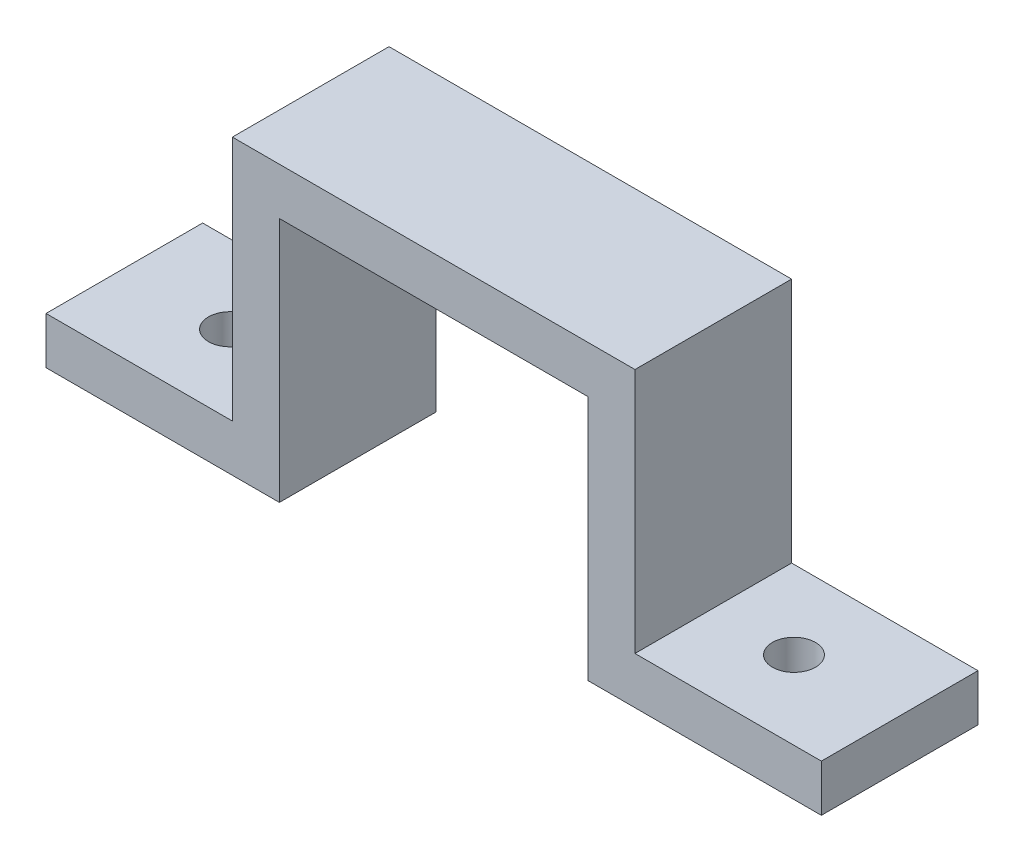
SolidWorks part; units mm, degrees
ref_plane "Front Plane" through (0, 0, 0) normal (0, 0, 1) x (1, 0, 0)
ref_plane "Top Plane" through (0, 0, 0) normal (0, 1, 0) x (1, 0, 0)
ref_plane "Right Plane" through (0, 0, 0) normal (1, 0, 0) x (0, 0, -1)
sketch "Sketch1" plane through (0, 0, 0) normal (0, 1, 0) x (1, 0, 0)
  line L0 (34.6, 0) -> (49.5, 0)
  line L1 (0, 0) -> (14.9, 0)
  line L2 (0, 0) -> (0, -10)
  line L3 (0, -10) -> (14.9, -10)
  line L4 (49.5, 0) -> (49.5, -10)
  line L5 (34.6, -10) -> (49.5, -10)
  line L6 (34.6, 0) -> (34.6, -10)
  line L11 (34.6, 0) -> (37.6, 0)
  line L12 (37.6, 0) -> (37.6, -10)
  line L13 (37.6, -10) -> (34.6, -10)
  line L21 (11.8988, 0) -> (11.8988, -10)
  line L22 (14.9, 0) -> (11.8988, 0)
  line L23 (14.9, 0) -> (14.9, -10)
  line L24 (11.8988, -10) -> (14.9, -10)
  circle A0 centre (6.75, -5) radius 1.375
  circle A1 centre (42.75, -5) radius 1.375
  dimension "D4" = 2.75
  dimension "D1" = 49.5
  dimension "D2" = 10
  dimension "D3" = 19.7
  dimension "D5" = 14.9
  dimension "D6" = 14.9
  dimension "D7" = 3.0012
  dimension "D8" = 3
extrude "Boss-Extrude1" add sketch "Sketch1" along normal blind 3 contours L1 L2 L3 A0 | L0 L12 L5 L4 A1 region at (43.55, 0, 0.1554) region at (5.9494, 0, 0.1554)
extrude "Boss-Extrude2" add sketch "Sketch1<4>" along normal blind 18.7 contours L1 L3 | L12 L0 L6 L5 region at (36.1, 0, 5) region at (13.3994, 0, 5)
sketch "Sketch1<4>" plane through (0, 0, 0) normal (0, 1, 0) x (1, 0, 0) same geometry as "Sketch1"
sketch "Sketch3" plane through (14.9, 0, 0) normal (1, 0, 0) x (0, 0, -1)
  line L1 (-10, 18.7) -> (0, 18.7)
  line L2 (-10, 18.7) -> (-10, 15.7)
  line L3 (-10, 15.7) -> (0, 15.7)
  line L4 (0, 18.7) -> (0, 15.7)
  dimension "D1" = 3
extrude "Boss-Extrude3" add sketch "Sketch3" along normal up to next
